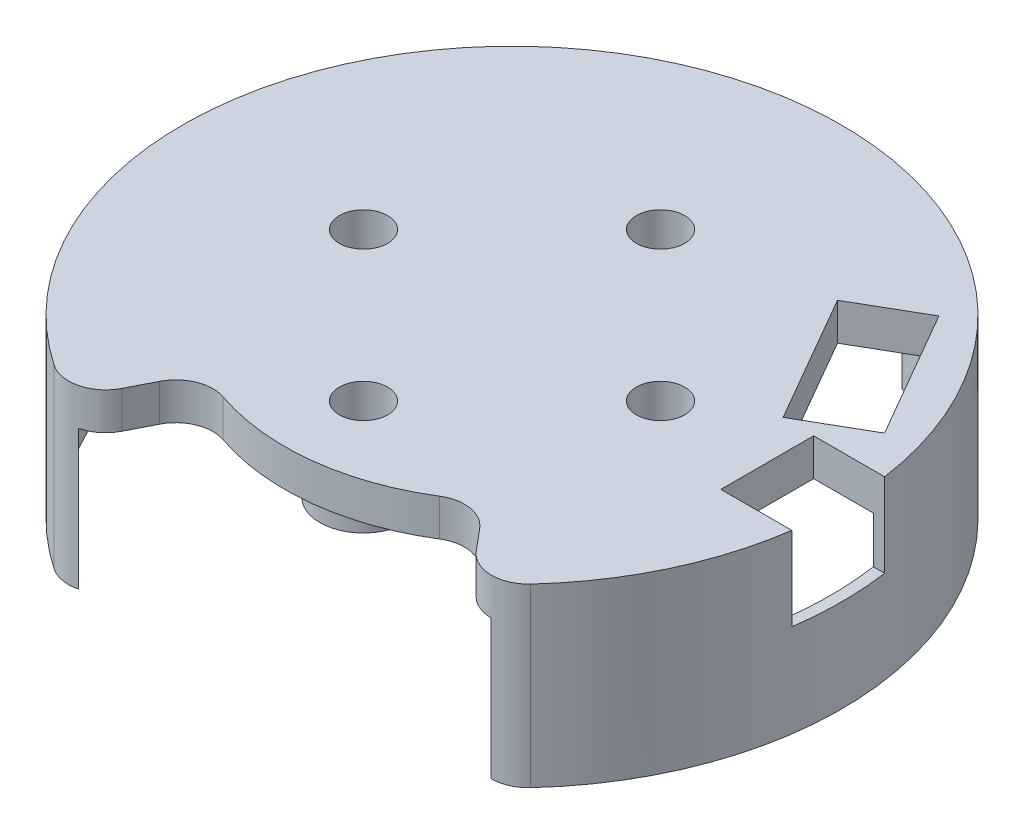
SolidWorks part; units mm, degrees
ref_plane "前视基准面" through (0, 0, 0) normal (0, 0, 1) x (1, 0, 0)
ref_plane "上视基准面" through (0, 0, 0) normal (0, 1, 0) x (1, 0, 0)
ref_plane "右视基准面" through (0, 0, 0) normal (1, 0, 0) x (0, 0, -1)
other "Configuration Table"
sketch "草图1" plane through (0, 0, 0) normal (0, 1, 0) x (1, 0, 0)
  circle A0 centre (0, 8) radius 1.3
  circle A1 centre (0, 0) radius 8 construction
  circle A2 centre (0, 8) radius 2.35
  circle A3 centre (8, 0) radius 1.3
  circle A4 centre (8, 0) radius 2.35
  circle A5 centre (0, -8) radius 1.3
  circle A6 centre (0, -8) radius 2.35
  circle A7 centre (-8, 0) radius 1.3
  circle A8 centre (-8, 0) radius 2.35
  point P18 (0, 0)
  dimension "D1" = 2.6
  dimension "D2" = 16
  dimension "D3" = 4.7
  dimension "D4" = 4
extrude "凸台-拉伸1" add sketch "草图1" along normal blind 2.5
sketch "草图2" plane through (0, 2.5, 0) normal (0, 1, 0) x (1, 0, 0)
  circle A0 centre (0, 0) radius 17.75
  dimension "D1" = 35.5
extrude "凸台-拉伸2" add sketch "草图2" along normal blind 2
sketch "草图3" plane through (0, 2.5, 0) normal (0, -1, 0) x (1, 0, 0)
  circle A0 centre (0, -8) radius 1.3 construction
  circle A1 centre (8, 0) radius 1.3 construction
  circle A2 centre (0, 8) radius 1.3 construction
  circle A3 centre (-8, 0) radius 1.3 construction
  circle A4 centre (0, -8) radius 1.3
  circle A5 centre (8, 0) radius 1.3
  circle A6 centre (0, 8) radius 1.3
  circle A7 centre (-8, 0) radius 1.3
extrude "切除-拉伸1" cut sketch "草图3" against normal through all
sketch "草图4" plane through (0, 4.5, 0) normal (0, 1, 0) x (1, 0, 0)
  line L0 (8.0679, 9.4641) -> (12.0679, 2.5359)
  line L1 (12.0679, 2.5359) -> (15.5321, 4.5359)
  line L2 (15.5321, 4.5359) -> (11.5321, 11.4641)
  line L3 (11.5321, 11.4641) -> (8.0679, 9.4641)
  line L4 (11.5321, 11.4641) -> (12.0679, 2.5359) construction
  line L5 (8.0679, 9.4641) -> (15.5321, 4.5359) construction
  line L6 (11.9131, 10.3103) -> (13.3381, 7.8422) construction
  point P4 (11.8, 7)
  dimension "D1" = 11.8
  dimension "D2" = 7
  dimension "D3" = 4
  dimension "D4" = 8
extrude "切除-拉伸2" cut sketch "草图4" against normal through all and the other way through all
sketch "草图5" plane through (0, 2.5, 0) normal (0, -1, 0) x (1, 0, 0)
  circle A0 centre (0, 0) radius 17.15
  circle A1 centre (0, 0) radius 17.75 construction
  circle A2 centre (0, 0) radius 17.75
  dimension "D1" = 34.3
extrude "凸台-拉伸3" add sketch "草图5" along normal blind 7.5
sketch "草图6" plane through (0, 4.5, 0) normal (0, 1, 0) x (1, 0, 0)
  line L1 (13.75, 2.5) -> (17.75, 2.5)
  line L2 (13.75, 2.5) -> (13.75, -2.5)
  line L3 (13.75, -2.5) -> (17.75, -2.5)
  line L4 (17.75, 2.5) -> (17.75, -2.5)
  line L5 (13.75, 2.5) -> (17.75, -2.5) construction
  line L6 (13.75, -2.5) -> (17.75, 2.5) construction
  circle A0 centre (0, 0) radius 17.75 construction
  point P0 (15.75, 0)
  dimension "D1" = 4
  dimension "D2" = 5
extrude "切除-拉伸3" cut sketch "草图6" against normal blind 4.5
sketch "草图7" plane through (0, 4.5, 0) normal (0, 1, 0) x (1, 0, 0)
  line L0 (11.4095, -13.5973) -> (7.8741, -9.384)
  line L1 (-8.0583, -15.8154) -> (-5.5614, -10.9148)
  line L2 (0, 0) -> (0, -24.4412) construction
  arc A0 (-5.5614, -10.9148) -> (7.8741, -9.384) centre (0, 0) ccw
  arc A1 (17.5731, 2.5) -> (17.5731, -2.5) centre (0, 0) ccw construction
  arc A2 (-8.0583, -15.8154) -> (11.4095, -13.5973) centre (0, 0) ccw
  dimension "D3" = 5.5
  dimension "D1" = 40
  dimension "D2" = 27
extrude "切除-拉伸4" cut sketch "草图7" against normal through all
sketch "草图8" plane through (0, -5, 0) normal (0, -1, 0) x (1, 0, 0)
  line L0 (-4.594, -17.1452) -> (-4.4387, -16.5656)
  line L1 (4.4387, -16.5656) -> (4.594, -17.1452)
  line L2 (-7.7859, 15.2808) -> (-8.0583, 15.8154)
  line L3 (11.4095, 13.5973) -> (11.0238, 13.1377)
  line L4 (-7.7859, 15.2808) -> (-8.0583, 15.8154)
  line L5 (11.4095, 13.5973) -> (11.0238, 13.1377)
  line L6 (0, 0) -> (0, -14.0847) construction
  arc A2 (-8.0583, 15.8154) -> (11.4095, 13.5973) centre (0, 0) ccw
  arc A3 (-7.7859, 15.2808) -> (11.0238, 13.1377) centre (0, 0) ccw
  arc A4 (-4.594, -17.1452) -> (4.594, -17.1452) centre (0, 0) ccw
  arc A5 (-4.4387, -16.5656) -> (4.4387, -16.5656) centre (0, 0) ccw
  dimension "D2" = 15
  dimension "D1" = 0
extrude "切除-拉伸5" cut sketch "草图8" against normal blind 3.5 contours A4 L1 A5 L0
fillet "圆角1" radius 2 4 edges at (-8.0583, -0.25, 15.8154) (11.4095, -0.25, 13.5973) (-5.5614, 3.5, 10.9148) (7.8741, 3.5, 9.384)
